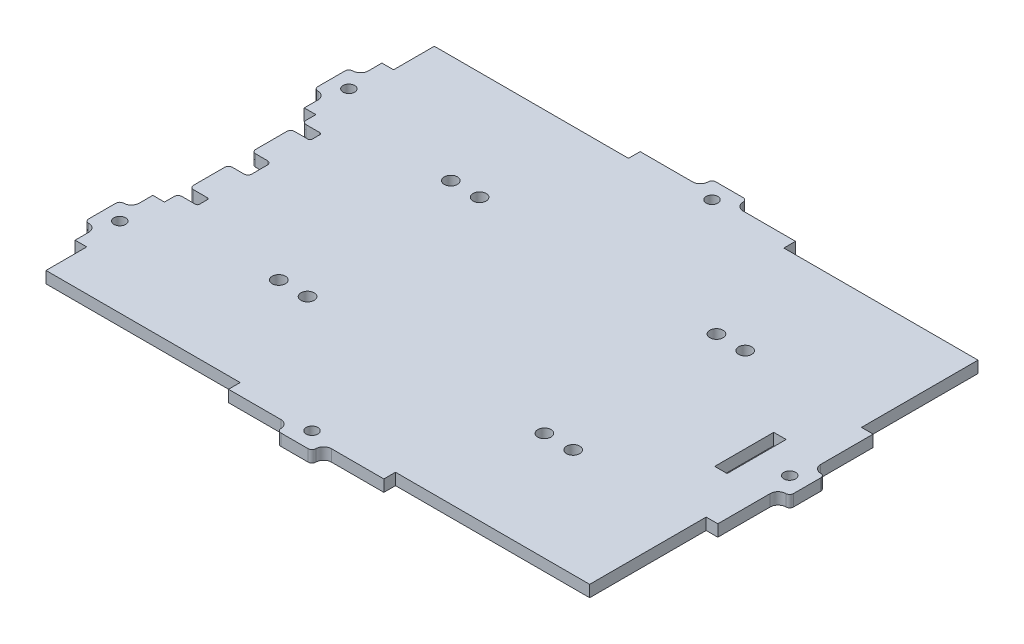
SolidWorks part; units mm, degrees
material "Acrylic (Medium-high impact)"
ref_plane "Plano frontal" through (0, 0, 0) normal (0, 0, 1) x (1, 0, 0)
ref_plane "Plano superior" through (0, 0, 0) normal (0, 1, 0) x (1, 0, 0)
ref_plane "Plano direito" through (0, 0, 0) normal (1, 0, 0) x (0, 0, -1)
sketch "Esboço1" plane through (0, 0, 0) normal (0, 1, 0) x (1, 0, 0)
  line L1 (-70, -50) -> (70, -50)
  line L2 (-70, -50) -> (-70, 50)
  line L3 (-70, 50) -> (70, 50)
  line L4 (70, -50) -> (70, 50)
  line L5 (-70, -50) -> (70, 50) construction
  line L6 (-70, 50) -> (70, -50) construction
  point P0 (0, 0)
  dimension "D1" = 140
  dimension "D2" = 100
extrude "Ressalto-extrusão1" add sketch "Esboço1" along normal mid plane 3
sketch "Esboço4" plane through (0, 1.5, 0) normal (0, 1, 0) x (1, 0, 0)
  line L5 (0, 0) -> (-70, 0) construction
  line L21 (6.5, 53) -> (20, 53)
  line L26 (-4.5, 56) -> (4.5, 56)
  line L27 (-4.5, 56) -> (-4.5, 55)
  line L42 (70, 50) -> (-70, 50) construction
  line L43 (-20, 50) -> (20, 50)
  line L44 (-20, 50) -> (-20, 53)
  line L45 (-20, 53) -> (-6.5, 53)
  line L46 (20, 50) -> (20, 53)
  line L48 (4.5, 56) -> (4.5, 55)
  line L49 (-1.65, 0) -> (1.65, 0) construction
  line L50 (4.5, -56) -> (4.5, -55)
  line L51 (20, -50) -> (20, -53)
  line L52 (-20, -53) -> (-6.5, -53)
  line L53 (-20, -50) -> (-20, -53)
  line L54 (-20, -50) -> (20, -50)
  line L55 (-4.5, -56) -> (-4.5, -55)
  line L56 (-4.5, -56) -> (4.5, -56)
  line L57 (6.5, -53) -> (20, -53)
  line L58 (70, -50) -> (70, 50) construction
  line L59 (70, 20) -> (73, 20)
  line L60 (70, 20) -> (70, -20)
  line L61 (70, -20) -> (73, -20)
  line L62 (73, 20) -> (73, 6.5)
  line L63 (73, -6.5) -> (73, -20)
  line L64 (75, 4.5) -> (76, 4.5)
  line L66 (75, -4.5) -> (76, -4.5)
  line L67 (76, 4.5) -> (76, -4.5)
  line L68 (-70, 50) -> (-70, -50) construction
  line L69 (-70, 39.5) -> (-73, 39.5)
  line L70 (-70, 39.5) -> (-70, 19.5)
  line L71 (-70, 19.5) -> (-73, 19.5)
  line L72 (-73, 39.5) -> (-73, 36)
  line L78 (-73, 23) -> (-73, 19.5)
  line L79 (-75, 34) -> (-76, 34)
  line L81 (-75, 25) -> (-76, 25)
  line L82 (-76, 34) -> (-76, 25)
  line L83 (-76, -34) -> (-76, -25)
  line L84 (-75, -25) -> (-76, -25)
  line L85 (-75, -34) -> (-76, -34)
  line L86 (-73, -23) -> (-73, -19.5)
  line L87 (-73, -39.5) -> (-73, -36)
  line L88 (-70, -19.5) -> (-73, -19.5)
  line L89 (-70, -39.5) -> (-70, -19.5)
  line L90 (-70, -39.5) -> (-73, -39.5)
  circle A6 centre (0, 51.5) radius 1.5 construction
  arc A7 (6.5, 53) -> (4.5, 55) centre (6.5, 55) cw
  arc A8 (-4.5, 55) -> (-6.5, 53) centre (-6.5, 55) cw
  circle A9 centre (0, -51.5) radius 1.5 construction
  arc A10 (-4.5, -55) -> (-6.5, -53) centre (-6.5, -55) ccw
  arc A11 (6.5, -53) -> (4.5, -55) centre (6.5, -55) ccw
  arc A12 (73, -6.5) -> (75, -4.5) centre (75, -6.5) cw
  arc A13 (75, 4.5) -> (73, 6.5) centre (75, 6.5) cw
  arc A14 (-73, 23) -> (-75, 25) centre (-75, 23) ccw
  arc A15 (-75, 34) -> (-73, 36) centre (-75, 36) ccw
  arc A16 (-75, -34) -> (-73, -36) centre (-75, -36) cw
  arc A17 (-73, -23) -> (-75, -25) centre (-75, -23) cw
  point P16 (76, 0)
  point P20 (73, 4.5)
  point P21 (70, 0)
  point P38 (-76, 29.5)
  point P39 (-70, 29.5)
  point P42 (0, 50)
  point P51 (4.5, 53)
  point P70 (4.5, -53)
  dimension "D2" = 9
  dimension "D6" = 2
  dimension "D8" = 3
  dimension "D9" = 3
  dimension "D11" = 2
  dimension "D14" = 2
  dimension "D3" = 40
  dimension "D4" = 9
  dimension "D5" = 3
  dimension "D7" = 19.5
  dimension "D10" = 3
  dimension "D12" = 20
  dimension "D13" = 9
  dimension "D15" = 3
  dimension "D16" = 10.5
extrude "Ressalto-extrusão2" add sketch "Esboço4" against normal through all
sketch "Esboço2" plane through (0, 1.5, 0) normal (0, 1, 0) x (1, 0, 0)
  line L32 (-20, -53) -> (-6.5, -53) construction
  line L51 (76, -4.5) -> (76, 4.5) construction
  line L64 (-70, 39.5) -> (-70, 19.5) construction
  line L89 (-76, 29.5) -> (-70, 29.5) construction
  line L90 (-4.5, -56) -> (4.5, -56) construction
  line L91 (-1.65, 0) -> (1.65, 0) construction
  line L94 (-76, 34) -> (-76, 25) construction
  line L95 (-73, 39.5) -> (-73, 36) construction
  circle A8 centre (0, -51.5) radius 1.5
  circle A9 centre (0, 51.5) radius 1.5
  circle A11 centre (71.5, 0) radius 1.5
  circle A12 centre (-71.5, 29.5) radius 1.5
  circle A13 centre (-71.5, -29.5) radius 1.5
  dimension "D1" = 3
  dimension "D2" = 3
  dimension "D3" = 3
  dimension "D4" = 3
extrude "Corte-extrusão1" cut sketch "Esboço2" against normal through all
sketch "Sketch1" plane through (0, 1.5, 0) normal (0, 1, 0) x (1, 0, 0)
  line L0 (-1.65, 0) -> (1.65, 0) construction
  line L1 (0, -1.65) -> (0, 1.65) construction
  circle A0 centre (30.5, -22.15) radius 1.7 construction
  circle A1 centre (30.5, -22.15) radius 1.7
  circle A2 centre (37.9, -22.15) radius 1.7 construction
  circle A3 centre (37.9, -22.15) radius 1.7
  circle A4 centre (37.9, 22.15) radius 1.7
  circle A5 centre (30.5, 22.15) radius 1.7
  circle A6 centre (-30.5, 22.15) radius 1.7
  circle A7 centre (-37.9, 22.15) radius 1.7
  circle A8 centre (-37.9, -22.15) radius 1.7
  circle A9 centre (-30.5, -22.15) radius 1.7
extrude "Cut-Extrude1" cut sketch "Sketch1" against normal through all both and the other way through all
sketch "Sketch3" plane through (0, 0, 0) normal (0, 1, 0) x (1, 0, 0)
  line L0 (-70, 19.5) -> (-70, -19.5) construction
  line L1 (-70, 3) -> (-66, 3)
  line L2 (-70, 3) -> (-70, -3)
  line L3 (-70, -3) -> (-66, -3)
  line L4 (-65, 2) -> (-65, -2)
  line L5 (-70, -48) -> (-70, 48) construction
  line L6 (-70, 16) -> (-65.5, 16)
  line L7 (-70, 16) -> (-70, 13)
  line L8 (-70, 13) -> (-65.5, 13)
  line L9 (-65, 15.5) -> (-65, 13.5)
  line L12 (-73, 19.5) -> (-70, 19.5) construction
  line L13 (-1.65, 0) -> (1.65, 0) construction
  line L14 (-65, -15.5) -> (-65, -13.5)
  line L15 (-70, -13) -> (-65.5, -13)
  line L16 (-70, -16) -> (-70, -13)
  line L17 (-70, -16) -> (-65.5, -16)
  arc A0 (-66, -3) -> (-65, -2) centre (-66, -2) ccw
  arc A1 (-66, 3) -> (-65, 2) centre (-66, 2) cw
  arc A2 (-65.5, 16) -> (-65, 15.5) centre (-65.5, 15.5) cw
  arc A3 (-65.5, 13) -> (-65, 13.5) centre (-65.5, 13.5) ccw
  arc A4 (-65.5, -13) -> (-65, -13.5) centre (-65.5, -13.5) cw
  arc A5 (-65.5, -16) -> (-65, -15.5) centre (-65.5, -15.5) ccw
  point P8 (-70, 0)
  point P14 (-65, 3)
  point P19 (-70, 14.5)
  point P24 (-65, 16)
  point P27 (-65, 13)
  point P38 (-65, -13)
  point P39 (-65, -16)
  dimension "D3" = 1
  dimension "D6" = 0.5
  dimension "D1" = 6
  dimension "D2" = 5
  dimension "D4" = 5
  dimension "D5" = 3
extrude "Cut-Extrude4" cut sketch "Sketch3" against normal through all both and the other way through all
fillet "Fillet1" radius 1 16 edges at (-4.5, 0, -56) (4.5, 0, -56) (4.5, 0, 56) (-4.5, 0, 56) (76, 0, 4.5) (76, 0, -4.5) (-76, 0, 25) (-76, 0, 34) (-76, 0, -25) (-76, 0, -34) (-70, 0, 3) (-70, 0, -3) (-70, 0, -16) (-70, 0, -13) (-70, 0, 16) (-70, 0, 13)
sketch "Sketch2" plane through (0, 0, 0) normal (0, 1, 0) x (1, 0, 0)
  line L0 (59.8, 7.6) -> (63, 7.6)
  line L1 (59.9, 7.5) -> (62.9, 7.5) construction
  line L2 (59.9, 7.5) -> (59.9, -7.5) construction
  line L3 (59.9, -7.5) -> (62.9, -7.5) construction
  line L4 (62.9, 7.5) -> (62.9, -7.5) construction
  line L5 (63, 7.6) -> (63, -7.6)
  line L6 (59.8, -7.6) -> (63, -7.6)
  line L7 (59.8, 7.6) -> (59.8, -7.6)
  line L8 (70, 20) -> (70, 50) construction
  line L10 (42, 12.5) -> (67, 12.5) construction
  line L11 (42, 12.5) -> (42, -12.5) construction
  line L12 (42, -12.5) -> (67, -12.5) construction
  line L13 (67, 12.5) -> (67, -12.5) construction
  line L14 (48, 9) -> (53, 9) construction
  line L15 (48, 9) -> (48, -9) construction
  line L16 (48, -9) -> (53, -9) construction
  line L17 (53, 9) -> (53, -9) construction
  point P4 (62.9, 0)
  point P10 (63, 0)
  point P17 (59.8, 0)
  point P18 (42, 0)
  point P21 (48, 0)
  dimension "D1" = 15
  dimension "D2" = 3
  dimension "D4" = 5
  dimension "D5" = 25
  dimension "D6" = 4
  dimension "D7" = 25
  dimension "D8" = 6
  dimension "D9" = 18
  dimension "D10" = 3
  dimension "D3" = 0.1
extrude "Cut-Extrude3" cut sketch "Sketch2" against normal through all both and the other way through all
